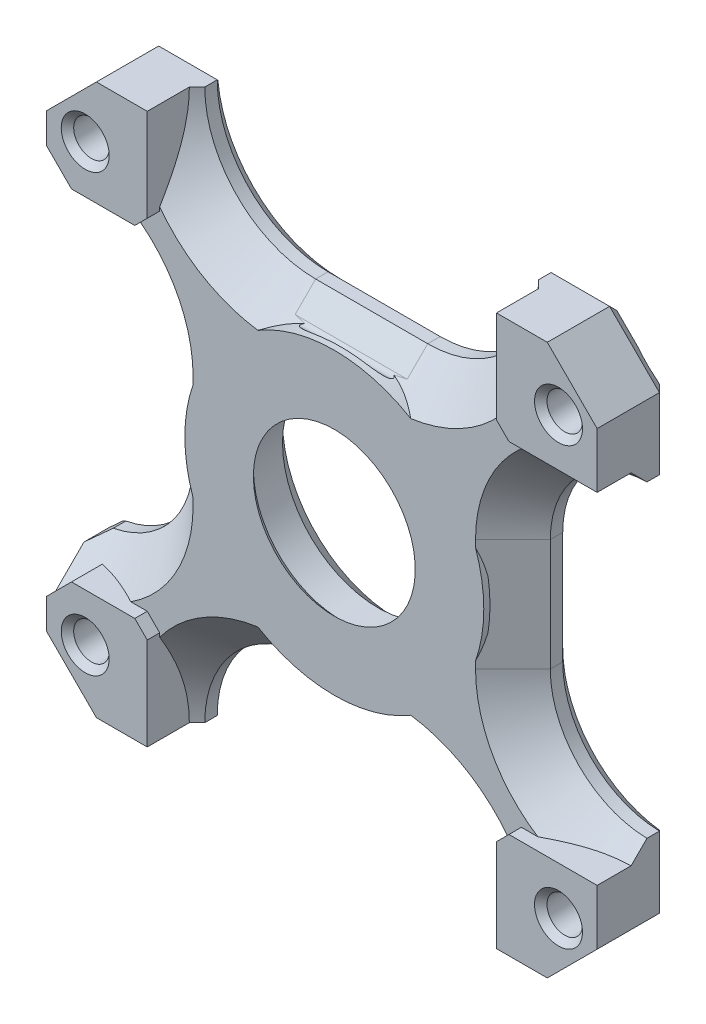
SolidWorks part; units mm, degrees
material "ABS"
ref_plane "Alzado" through (0, 0, 0) normal (0, 0, 1) x (1, 0, 0)
ref_plane "Planta" through (0, 0, 0) normal (0, 1, 0) x (1, 0, 0)
ref_plane "Vista lateral" through (0, 0, 0) normal (1, 0, 0) x (0, 0, -1)
sketch "Croquis1" plane through (0, 0, 0) normal (0, 0, 1) x (1, 0, 0)
  line L1 (22.1, 22.1) -> (-22.1, 22.1)
  line L2 (22.1, 22.1) -> (22.1, -22.1)
  line L3 (22.1, -22.1) -> (-22.1, -22.1)
  line L4 (-22.1, 22.1) -> (-22.1, -22.1)
  line L5 (22.1, 22.1) -> (-22.1, -22.1) construction
  line L6 (22.1, -22.1) -> (-22.1, 22.1) construction
  circle A0 centre (0, 0) radius 7.66
  point P0 (0, 0)
  dimension "D1" = 15.32
  dimension "D2" = 44.2
  dimension "D3" = 44.2
extrude "Saliente-Extruir1" add sketch "Croquis1" along normal blind 5
chamfer "Chaflán2" distance 4 angle 45 4 edges at (-22.1, 22.1, 2.5) (22.1, 22.1, 2.5) (-22.1, -22.1, 2.5) (22.1, -22.1, 2.5)
sketch "Croquis2" plane through (0, 0, 5) normal (0, 0, 1) x (1, 0, 0)
  line L1 (19, -17.5) -> (-19, -17.5) construction
  line L2 (19, -17.5) -> (19, 17.5) construction
  line L3 (19, 17.5) -> (-19, 17.5) construction
  line L4 (-19, -17.5) -> (-19, 17.5) construction
  line L5 (19, -17.5) -> (-19, 17.5) construction
  line L6 (19, 17.5) -> (-19, -17.5) construction
  circle A0 centre (-19, -17.5) radius 1.425
  circle A1 centre (19, -17.5) radius 1.425
  circle A2 centre (19, 17.5) radius 1.425
  circle A3 centre (-19, 17.5) radius 1.425
  point P0 (0, 0)
  dimension "D1" = 2.85
  dimension "D2" = 38
  dimension "D3" = 35
extrude "Cortar-Extruir1" cut sketch "Croquis2" against normal through all
sketch "Croquis3" plane through (0, 0, 5) normal (0, 0, 1) x (1, 0, 0)
  line L0 (0, 0) -> (0, 8.674) construction
  line L1 (-5.4698, 0) -> (5.6627, 0) construction
  line L2 (-4.5, -22.1) -> (4.5, -22.1) construction
  line L5 (-18.1, -22.1) -> (18.1, -22.1) construction
  line L8 (-22.2262, 4.5) -> (-22.2262, -4.5) construction
  line L9 (-14.3382, 4.5) -> (-14.3382, -4.5)
  line L10 (-30.1142, 4.5) -> (-30.1142, -4.5)
  line L11 (22.2262, 4.5) -> (22.2262, -4.5) construction
  line L12 (14.3382, 4.5) -> (14.3382, -4.5)
  line L13 (30.1142, 4.5) -> (30.1142, -4.5)
  line L14 (-4.5, -13.2) -> (4.5, -13.2)
  line L15 (-4.5, -31) -> (4.5, -31)
  line L16 (-4.5, 22.1) -> (4.5, 22.1) construction
  line L17 (-4.5, 13.2) -> (4.5, 13.2)
  line L18 (-4.5, 31) -> (4.5, 31)
  arc A8 (-14.3382, 4.5) -> (-30.1142, 4.5) centre (-22.2262, 4.5) ccw
  arc A9 (-30.1142, -4.5) -> (-14.3382, -4.5) centre (-22.2262, -4.5) ccw
  arc A10 (14.3382, 4.5) -> (30.1142, 4.5) centre (22.2262, 4.5) cw
  arc A11 (30.1142, -4.5) -> (14.3382, -4.5) centre (22.2262, -4.5) cw
  arc A12 (-4.5, -13.2) -> (-4.5, -31) centre (-4.5, -22.1) ccw
  arc A13 (4.5, -31) -> (4.5, -13.2) centre (4.5, -22.1) ccw
  arc A14 (-4.5, 13.2) -> (-4.5, 31) centre (-4.5, 22.1) cw
  arc A15 (4.5, 31) -> (4.5, 13.2) centre (4.5, 22.1) cw
  point P13 (0, -22.1)
  point P16 (-22.2262, 0)
  point P28 (0, 22.1)
  point P31 (22.2262, 0)
  dimension "D1" = 9
  dimension "D2" = 9
extrude "Cortar-Extruir2" cut sketch "Croquis3" against normal through all
chamfer "Chaflán4" distance 1 angle 45 24 edges at (-20.1, -20.1, 0) (-22.1, -15.2435, 0) (-22.1, 15.2435, 0) (-20.1, 20.1, 0) (-15.75, 22.1, 0) (15.75, 22.1, 0) (20.1, 20.1, 0) (22.1, 15.2435, 0) (22.1, -15.2435, 0) (20.1, -20.1, 0) (-15.75, -22.1, 0) (15.75, -22.1, 0) (16.6041, 10.0329, 0) (16.6041, -10.0329, 0) (14.3382, 0, 0) (-16.6041, -10.0329, 0) (-16.6041, 10.0329, 0) (-14.3382, 0, 0) (-10.7933, 15.8067, 0) (10.7933, 15.8067, 0) (0, 13.2, 0) (10.7933, -15.8067, 0) (-10.7933, -15.8067, 0) (0, -13.2, 0)
sketch "Croquis4" plane through (0, 0, 5) normal (0, 0, 1) x (1, 0, 0)
  line L0 (0, 9.5604) -> (0, -8.6044) construction
  line L1 (8.445, 0) -> (-7.3297, 0) construction
  line L2 (-22.1, -18.1) -> (-18.1, -22.1)
  line L3 (-18.1, -22.1) -> (-14.0196, -22.1)
  line L4 (-18.1, -22.1) -> (-13.4, -22.1) construction
  line L5 (-14.0196, -22.1) -> (-14.0196, -13.6606)
  line L6 (-14.0196, -13.6606) -> (-22.1, -13.6606)
  line L7 (-22.1, -12.387) -> (-22.1, -18.1) construction
  line L8 (-22.1, -13.6606) -> (-22.1, -18.1)
  line L9 (22.1, -13.6606) -> (22.1, -18.1)
  line L10 (14.0196, -13.6606) -> (22.1, -13.6606)
  line L11 (14.0196, -22.1) -> (14.0196, -13.6606)
  line L12 (18.1, -22.1) -> (14.0196, -22.1)
  line L13 (22.1, -18.1) -> (18.1, -22.1)
  line L14 (22.1, 18.1) -> (18.1, 22.1)
  line L15 (18.1, 22.1) -> (14.0196, 22.1)
  line L16 (14.0196, 22.1) -> (14.0196, 13.6606)
  line L17 (14.0196, 13.6606) -> (22.1, 13.6606)
  line L18 (22.1, 13.6606) -> (22.1, 18.1)
  line L19 (-22.1, 13.6606) -> (-22.1, 18.1)
  line L20 (-14.0196, 13.6606) -> (-22.1, 13.6606)
  line L21 (-14.0196, 22.1) -> (-14.0196, 13.6606)
  line L22 (-18.1, 22.1) -> (-14.0196, 22.1)
  line L23 (-22.1, 18.1) -> (-18.1, 22.1)
  circle A0 centre (-19, -17.5) radius 1.425
  circle A1 centre (-19, -17.5) radius 1.425 construction
  circle A2 centre (19, -17.5) radius 1.425
  circle A3 centre (19, 17.5) radius 1.425
  circle A4 centre (-19, 17.5) radius 1.425
extrude "Saliente-Extruir2" add sketch "Croquis4" along normal blind 1
chamfer "Chaflán5" distance 3 angle 45 20 edges at (-22.1, 13.0238, 5) (-22.1, -13.0238, 5) (22.1, -13.0238, 5) (22.1, 13.0238, 5) (-13.7098, -22.1, 5) (13.7098, -22.1, 5) (13.7098, 22.1, 5) (-13.7098, 22.1, 5) (-16.6041, -10.0329, 5) (-16.6041, 10.0329, 5) (-14.3382, 0, 5) (16.6041, 10.0329, 5) (16.6041, -10.0329, 5) (14.3382, 0, 5) (10.7933, -15.8067, 5) (-10.7933, -15.8067, 5) (0, -13.2, 5) (-10.7933, 15.8067, 5) (10.7933, 15.8067, 5) (0, 13.2, 5)
chamfer "Chaflán3" distance 0.5 angle 45 8 edges at (-17.575, 17.5, 0) (20.425, 17.5, 0) (20.425, -17.5, 0) (-17.575, -17.5, 0) (17.575, -17.5, 6) (20.425, 17.5, 6) (-20.425, 17.5, 6) (-17.575, -17.5, 6)
sketch "Croquis5" plane through (0, 0, 5) normal (0, 0, -1) x (-1, 0, 0)
  circle A0 centre (0, 0) radius 6
  circle A1 centre (0, 0) radius 12
  dimension "D1" = 12
  dimension "D2" = 24
extrude "Saliente-Extruir4" add sketch "Croquis5" along normal blind 0.5
chamfer "Chaflán6" distance 1.5 angle 45 1 edges at (7.66, 0, 0)
chamfer "Chaflán7" distance 1 angle 45 1 edges at (-6, 0, 4.5)
chamfer "Chaflán8" distance 2 angle 45 2 edges at (-22.1, 13.6606, 4.6367) (-22.1, -13.6606, 4.6367)
chamfer "Chaflán9" distance 1 angle 50 2 edges at (-22.1, 12.387, 1.5) (-22.1, -12.387, 1.5)
fillet "Redondeo2" radius 0.5 2 edges at (0, -10.7, 4.5) (0, 10.7, 4.5)
chamfer "Chaflán10" distance 1 angle 45 4 edges at (14.0196, 13.6606, 5.5) (-14.0196, 13.6606, 5.5) (14.0196, -13.6606, 5.5) (-14.0196, -13.6606, 5.5)
